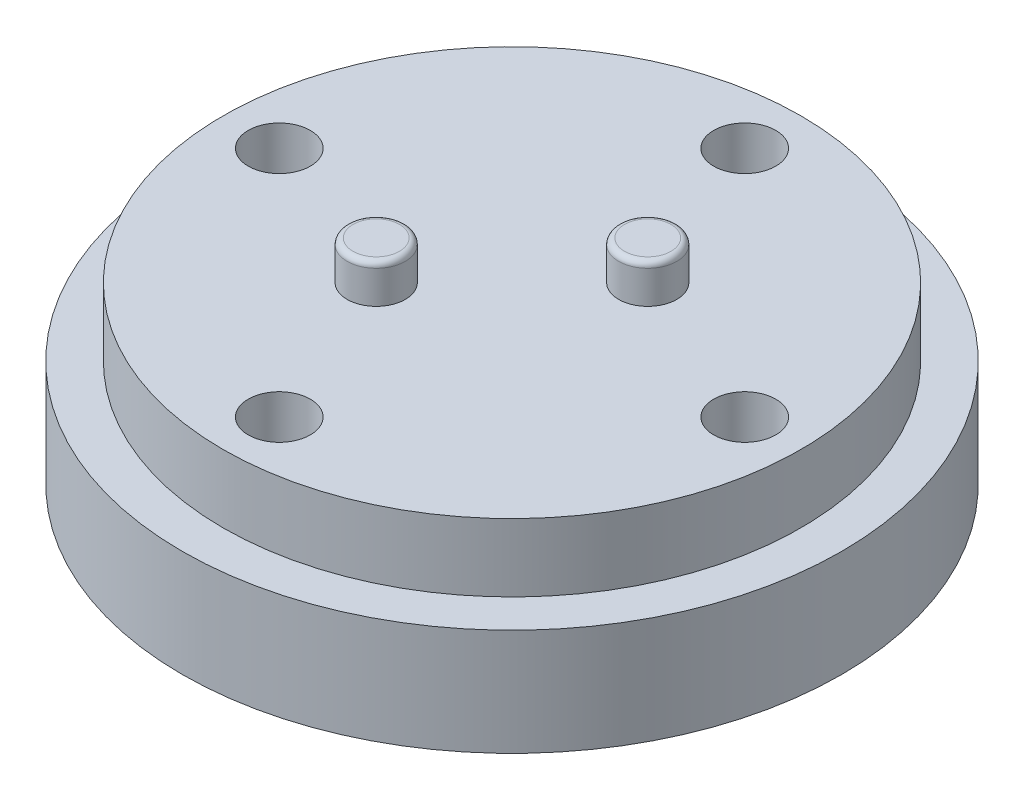
SolidWorks part; units mm, degrees
ref_plane "Front Plane" through (0, 0, 0) normal (0, 0, 1) x (1, 0, 0)
ref_plane "Top Plane" through (0, 0, 0) normal (0, 1, 0) x (1, 0, 0)
ref_plane "Right Plane" through (0, 0, 0) normal (1, 0, 0) x (0, 0, -1)
sketch "Sketch1" plane through (0, 0, 0) normal (0, 1, 0) x (1, 0, 0)
  circle A0 centre (0, 0) radius 14.9
  circle A1 centre (0, -12) radius 1.6
  circle A2 centre (-12, 0) radius 1.6
  circle A3 centre (0, 12) radius 1.6
  circle A4 centre (12, 0) radius 1.6
  circle A5 centre (3.5, 3.5) radius 1.5
  circle A6 centre (-3.5, -3.5) radius 1.5
  point P14 (0, 0)
  point P16 (0, 0)
  point P18 (-5.3117, -2.4353)
  dimension "D1" = 29.8
  dimension "D2" = 3.2
  dimension "D5" = 3
  dimension "D3" = 12
  dimension "D6" = 3.5
  dimension "D7" = 3.5
  dimension "D8" = 3.5
  dimension "D9" = 3.5
  dimension "D4" = 4
extrude "Boss-Extrude1" add sketch "Sketch1" along normal blind 3.5 contours A5 | A6 | A0 A6 A5 A4 A3 A2 A1 region at (0, 0, 0) region at (3.5, 0, -3.5) region at (-3.5, 0, 3.5)
extrude "Boss-Extrude2" add sketch "Sketch1<3>" along normal blind 2 from surface contours A6 | A5 region at (3.5, 0, -3.5) region at (-3.5, 0, 3.5) starting at face at (12, 3.5, 1.6)
sketch "Sketch1<3>" plane through (0, 0, 0) normal (0, 1, 0) x (1, 0, 0) same geometry as "Sketch1"
fillet "Fillet1" radius 0.3 2 edges at (3.5, 5.5, -2) (-3.5, 5.5, 5)
sketch "Sketch2" plane through (0, 0, 0) normal (0, -1, 0) x (1, 0, 0)
  circle A0 centre (0, 0) radius 17
  circle A1 centre (-12, 0) radius 1.6 construction
  circle A2 centre (0, -12) radius 1.6 construction
  circle A3 centre (12, 0) radius 1.6 construction
  circle A4 centre (0, 12) radius 1.6 construction
  circle A5 centre (-12, 0) radius 1.6
  circle A6 centre (0, -12) radius 1.6
  circle A7 centre (12, 0) radius 1.6
  circle A8 centre (0, 12) radius 1.6
  dimension "D1" = 34
extrude "Boss-Extrude3" add sketch "Sketch2" along normal blind 5.5
sketch "Sketch3" plane through (0, -5.5, 0) normal (0, -1, 0) x (1, 0, 0)
  line L0 (-4.1012, -1.4142) -> (-1.4142, -4.1012)
  line L1 (-4.1012, 1.4142) -> (-1.4142, 4.1012)
  line L2 (1.4142, -4.1012) -> (4.1012, -1.4142)
  line L3 (1.4142, 4.1012) -> (4.1012, 1.4142)
  arc A0 (4.1012, -1.4142) -> (4.1012, 1.4142) centre (2.687, 0) ccw
  arc A1 (-1.4142, -4.1012) -> (1.4142, -4.1012) centre (0, -2.687) ccw
  arc A2 (-4.1012, 1.4142) -> (-4.1012, -1.4142) centre (-2.687, 0) ccw
  arc A3 (-1.4142, 4.1012) -> (1.4142, 4.1012) centre (0, 2.687) cw
  point P0 (0, 5.5027)
  point P8 (5.5154, 0)
  point P11 (0, -5.5154)
  point P14 (-5.5154, 0)
  point P17 (0, 5.5154)
  dimension "D2" = 2
  dimension "D1" = 7.8
extrude "Boss-Extrude4" add sketch "Sketch3" along normal blind 3
fillet "Fillet2" radius 0.5 8 edges at (2.7577, -8.5, -2.7577) (0, -8.5, -4.687) (-2.7577, -8.5, -2.7577) (-4.687, -8.5, 0) (-2.7577, -8.5, 2.7577) (0, -8.5, 4.687) (2.7577, -8.5, 2.7577) (4.687, -8.5, 0)
